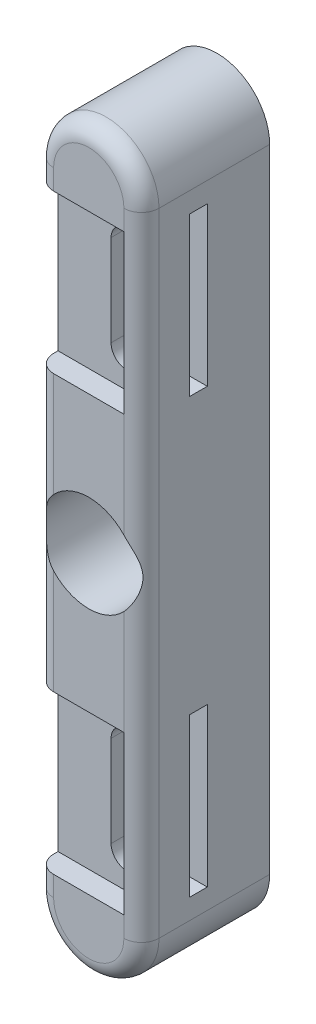
SolidWorks part; units mm, degrees
ref_plane "Alzado" through (0, 0, 0) normal (0, 0, 1) x (1, 0, 0)
ref_plane "Planta" through (0, 0, 0) normal (0, 1, 0) x (1, 0, 0)
ref_plane "Vista lateral" through (0, 0, 0) normal (1, 0, 0) x (0, 0, -1)
sketch "Croquis1" plane through (0, 0, 0) normal (0, 0, 1) x (1, 0, 0)
  line L0 (58.9, -7.25) -> (58.9, 64.75) construction
  line L1 (52.9, -7.25) -> (52.9, 64.75)
  line L2 (64.9, -7.25) -> (64.9, 64.75)
  line L3 (-29.1, 70.75) -> (64.9, 70.75) construction
  arc A0 (52.9, -7.25) -> (64.9, -7.25) centre (58.9, -7.25) ccw
  arc A1 (64.9, 64.75) -> (52.9, 64.75) centre (58.9, 64.75) ccw
  arc A3 (58.9, -13.25) -> (64.9, -7.25) centre (58.9, -7.25) ccw construction
  point P2 (0, 0)
  point P3 (58.9, 64.0696)
  point P4 (58.9, 28.75)
  dimension "D1" = 6
extrude "Saliente-Extruir1" add sketch "Croquis1" along normal up to surface (14.6 mm away) contours A0 L2 A1 L1
fillet "Redondeo1" radius 2 4 edges at (58.9, 70.75, 14.6) (64.9, 28.75, 14.6) (58.9, -13.25, 14.6) (52.9, 28.75, 14.6)
sketch "Croquis2" plane through (0, 0, 14.6) normal (0, 0, 1) x (1, 0, 0)
  line L0 (46.8348, -4.9448) -> (62.9, -4.9448)
  line L1 (46.8348, -4.9448) -> (46.8348, 13.0552)
  line L2 (62.9, -4.9448) -> (62.9, 13.0552)
  line L3 (46.8348, 13.0552) -> (62.9, 13.0552)
  line L5 (62.9, -7.25) -> (62.9, 64.75) construction
  line L6 (62.9, 28.75) -> (50062.9, 28.75) construction
  line L7 (62.9, 62.4448) -> (62.9, 44.4448)
  line L8 (46.8348, 44.4448) -> (62.9, 44.4448)
  line L9 (46.8348, 62.4448) -> (46.8348, 44.4448)
  line L10 (46.8348, 62.4448) -> (62.9, 62.4448)
  point P8 (62.9, 28.75)
  dimension "D1" = 18
extrude "Cortar-Extruir1" cut sketch "Croquis2" against normal blind 2.5
sketch "Croquis3" plane through (0, 0, 14.6) normal (0, 0, 1) x (1, 0, 0)
  line L0 (58.9, 64.75) -> (58.9, -7.25) construction
  circle A0 centre (58.9, 28.75) radius 5.5
  dimension "D1" = 11
extrude "Cortar-Extruir2" cut sketch "Croquis3" against normal through all contours A0
sketch "Croquis4" plane through (64.9, 0, 0) normal (1, 0, 0) x (0, 0, -1)
  line L0 (-14.6, 62.4448) -> (0, 62.4448) construction
  line L1 (0, 70.75) -> (0, -13.25) construction
  line L2 (-14.6, 44.4448) -> (0, 44.4448) construction
  line L3 (-14.6, 13.0552) -> (0, 13.0552) construction
  line L4 (-14.6, -4.9448) -> (0, -4.9448) construction
  line L5 (-12.6, 28.75) -> (0, 28.75) construction
  line L6 (-12.6, 64.75) -> (-12.6, -7.25) construction
  line L7 (-12.1, -4.9448) -> (-12.1, 13.0552) construction
  line L8 (-9.1, 13.0552) -> (-7.1, 13.0552)
  line L9 (-9.1, 13.0552) -> (-9.1, -4.9448)
  line L10 (-9.1, -4.9448) -> (-7.1, -4.9448)
  line L11 (-7.1, 13.0552) -> (-7.1, -4.9448)
  line L12 (-9.1, 62.4448) -> (-7.1, 62.4448)
  line L13 (-9.1, 44.4448) -> (-7.1, 44.4448)
  line L14 (-7.1, 44.4448) -> (-7.1, 62.4448)
  line L15 (-9.1, 44.4448) -> (-9.1, 62.4448)
  dimension "D1" = 3
  dimension "D2" = 2
extrude "Cortar-Extruir3" cut sketch "Croquis4" against normal blind 6.5
sketch "Croquis5" plane through (0, 0, 12.1) normal (0, 0, 1) x (1, 0, 0)
  line L0 (60.741, 9.2452) -> (60.741, 50009.2452) construction
  line L1 (52.9, 28.75) -> (64.9, 28.75) construction
  line L2 (52.9, 13.0552) -> (52.9, 44.4448) construction
  line L3 (64.9, 64.75) -> (64.9, -7.25) construction
  line L4 (60.741, 9.2452) -> (60.741, -1.1348) construction
  line L5 (62.541, 9.2452) -> (62.541, -1.1348)
  line L6 (58.941, 9.2452) -> (58.941, -1.1348)
  line L7 (62.9, 13.0552) -> (54.9, 13.0552) construction
  line L8 (60.741, 48.2548) -> (60.741, 58.6348) construction
  line L9 (62.541, 48.2548) -> (62.541, 58.6348)
  line L10 (58.941, 48.2548) -> (58.941, 58.6348)
  arc A0 (62.541, 9.2452) -> (58.941, 9.2452) centre (60.741, 9.2452) ccw
  arc A1 (58.941, -1.1348) -> (62.541, -1.1348) centre (60.741, -1.1348) ccw
  arc A2 (62.541, 48.2548) -> (58.941, 48.2548) centre (60.741, 48.2548) cw
  arc A3 (58.941, 58.6348) -> (62.541, 58.6348) centre (60.741, 58.6348) cw
  point P11 (60.741, 4.0552)
  point P25 (60.741, 53.4448)
  dimension "D1" = 1.8
  dimension "D2" = 10.38
  dimension "D3" = 3.81
extrude "Cortar-Extruir4" cut sketch "Croquis5" against normal through all
